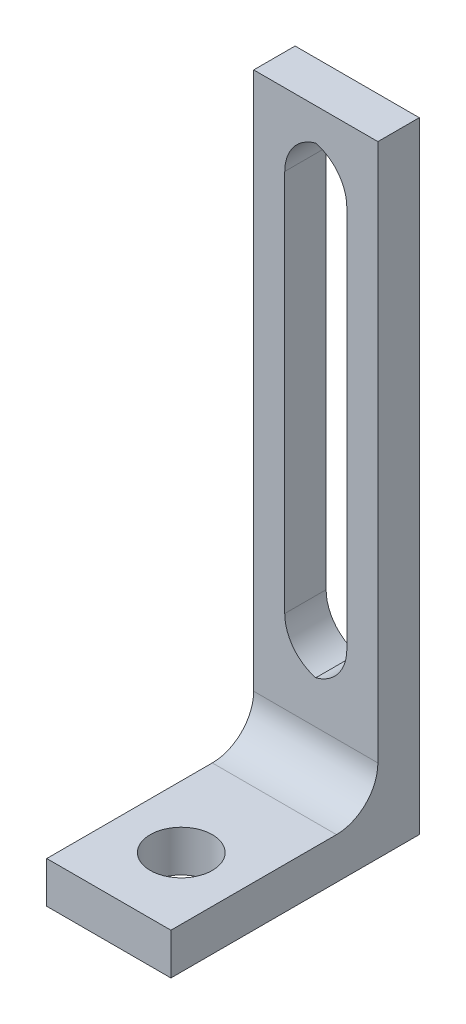
SolidWorks part; units mm, degrees
ref_plane "Front Plane" through (0, 0, 0) normal (0, 0, 1) x (1, 0, 0)
ref_plane "Top Plane" through (0, 0, 0) normal (0, 1, 0) x (1, 0, 0)
ref_plane "Right Plane" through (0, 0, 0) normal (1, 0, 0) x (0, 0, -1)
sketch "Sketch1" plane through (0, 0, 0) normal (0, 0, 1) x (1, 0, 0)
  line L1 (-3, 15) -> (3, 15)
  line L2 (-3, 15) -> (-3, -15)
  line L3 (-3, -15) -> (3, -15)
  line L4 (3, 15) -> (3, -15)
  line L5 (-3, 15) -> (3, -15) construction
  line L6 (-3, -15) -> (3, 15) construction
  line L7 (-1.5, 13.5) -> (1.5, 13.5)
  line L8 (-1.5, 13.5) -> (-1.5, -9)
  line L9 (-1.5, -9) -> (1.5, -9)
  line L10 (1.5, 13.5) -> (1.5, -9)
  line L11 (-1.5, 13.5) -> (1.5, -9) construction
  line L12 (-1.5, -9) -> (1.5, 13.5) construction
  point P0 (0, 0)
  point P6 (0, 2.25)
  dimension "D1" = 30
  dimension "D2" = 6
  dimension "D3" = 1.5
  dimension "D4" = 3
  dimension "D5" = 22.5
  dimension "D6" = 1.5
extrude "Boss-Extrude1" add sketch "Sketch1" along normal blind 2
fillet "Fillet1" radius 2 4 edges at (1.5, 13.5, 1) (-1.5, 13.5, 1) (1.5, -9, 1) (-1.5, -9, 1)
sketch "Sketch2" plane through (0, 0, 2) normal (0, 0, 1) x (1, 0, 0)
  line L0 (3, -15) -> (3, 15) construction
  line L1 (-3, -15) -> (3, -15)
  line L2 (-3, -15) -> (-3, -13)
  line L3 (-3, -13) -> (3, -13)
  line L4 (3, -15) -> (3, -13)
  dimension "D1" = 2
extrude "Boss-Extrude2" add sketch "Sketch2" along normal blind 10
fillet "Fillet2" radius 2 1 edges at (0, -13, 2)
sketch "Sketch3" plane through (0, -13, 0) normal (0, 1, 0) x (1, 0, 0)
  line L0 (3, -12) -> (-3, -12) construction
  line L2 (-3, -12) -> (-3, -4) construction
  circle A0 centre (0, -8.5) radius 1.5
  point P6 (3, -8.0918)
  dimension "D1" = 3
  dimension "D2" = 3.5
  dimension "D3" = 3
extrude "Cut-Extrude1" cut sketch "Sketch3" against normal blind 10
